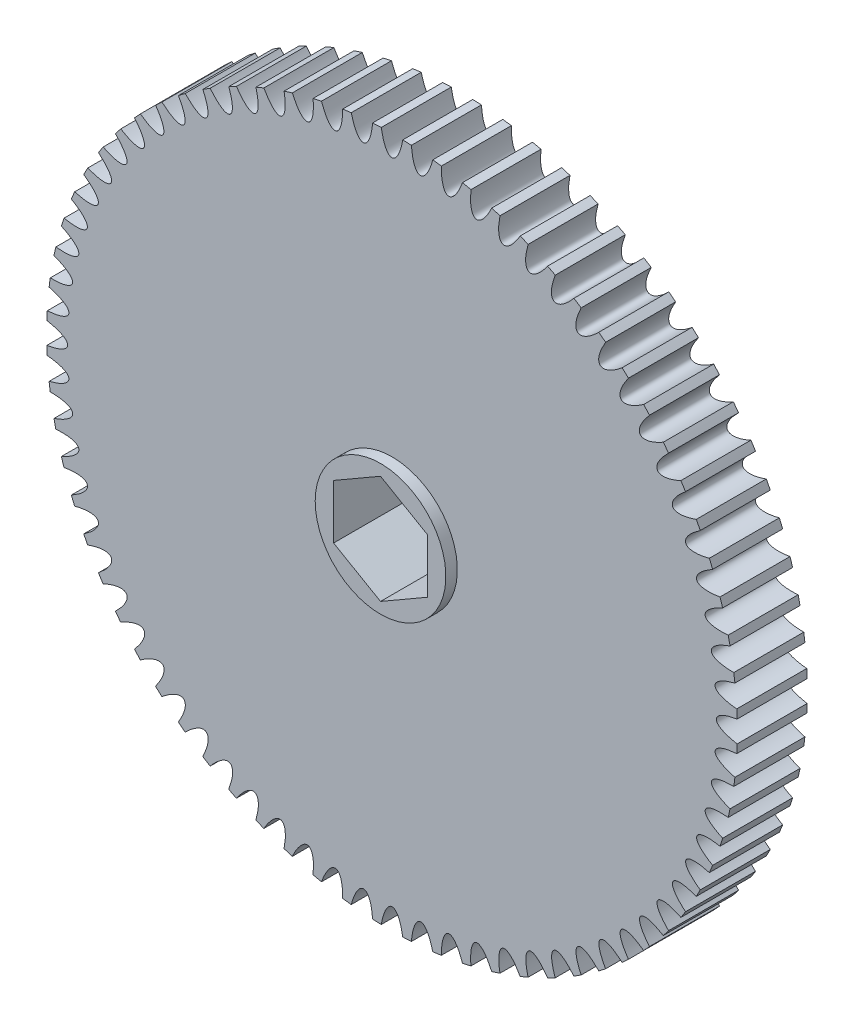
SolidWorks part; units mm, degrees
material "Vex Aluminum Spur Gear"
ref_plane "Front Plane" through (0, 0, 0) normal (0, 0, 1) x (1, 0, 0)
ref_plane "Top Plane" through (0, 0, 0) normal (0, 1, 0) x (1, 0, 0)
ref_plane "Right Plane" through (0, 0, 0) normal (1, 0, 0) x (0, 0, -1)
ref_plane "Plane1" through (0, 0, -4.7625) normal (0, 0, -1) x (-1, 0, 0)
sketch "Sketch1" plane through (0, 0, -4.7625) normal (0, 0, -1) x (-1, 0, 0)
  arc A0 (-46.916, 2.6363) -> (-46.9672, 1.4627) centre (0, 0) ccw
  arc A1 (-46.9672, -1.4627) -> (-46.916, -2.6363) centre (0, 0) ccw
  arc A2 (-46.661, -5.5506) -> (-46.5077, -6.7153) centre (0, 0) ccw
  arc A3 (-45.9997, -9.5963) -> (-45.7454, -10.7431) centre (0, 0) ccw
  arc A4 (-44.9883, -13.5689) -> (-44.635, -14.6892) centre (0, 0) ccw
  arc A5 (-43.6345, -17.4382) -> (-43.1849, -18.5235) centre (0, 0) ccw
  arc A6 (-41.9486, -21.1749) -> (-41.4062, -22.2169) centre (0, 0) ccw
  arc A7 (-39.9435, -24.7504) -> (-39.3123, -25.7411) centre (0, 0) ccw
  arc A8 (-37.6343, -28.1375) -> (-36.9192, -29.0694) centre (0, 0) ccw
  arc A9 (-35.0388, -31.3105) -> (-34.2451, -32.1765) centre (0, 0) ccw
  arc A10 (-32.1765, -34.2451) -> (-31.3105, -35.0388) centre (0, 0) ccw
  arc A11 (-29.0694, -36.9192) -> (-28.1375, -37.6343) centre (0, 0) ccw
  arc A12 (-25.7411, -39.3123) -> (-24.7504, -39.9435) centre (0, 0) ccw
  arc A13 (-22.2169, -41.4062) -> (-21.1749, -41.9486) centre (0, 0) ccw
  arc A14 (-18.5235, -43.1849) -> (-17.4382, -43.6345) centre (0, 0) ccw
  arc A15 (-14.6892, -44.635) -> (-13.5689, -44.9883) centre (0, 0) ccw
  arc A16 (-10.7431, -45.7454) -> (-9.5963, -45.9997) centre (0, 0) ccw
  arc A17 (-6.7153, -46.5077) -> (-5.5506, -46.661) centre (0, 0) ccw
  arc A18 (-2.6363, -46.916) -> (-1.4627, -46.9672) centre (0, 0) ccw
  arc A19 (1.4627, -46.9672) -> (2.6363, -46.916) centre (0, 0) ccw
  arc A20 (5.5506, -46.661) -> (6.7153, -46.5077) centre (0, 0) ccw
  arc A21 (9.5963, -45.9997) -> (10.7431, -45.7454) centre (0, 0) ccw
  arc A22 (13.5689, -44.9883) -> (14.6892, -44.635) centre (0, 0) ccw
  arc A23 (17.4382, -43.6345) -> (18.5235, -43.1849) centre (0, 0) ccw
  arc A24 (21.1749, -41.9486) -> (22.2169, -41.4062) centre (0, 0) ccw
  arc A25 (24.7504, -39.9435) -> (25.7411, -39.3123) centre (0, 0) ccw
  arc A26 (28.1375, -37.6343) -> (29.0694, -36.9192) centre (0, 0) ccw
  arc A27 (31.3105, -35.0388) -> (32.1765, -34.2451) centre (0, 0) ccw
  arc A28 (34.2451, -32.1765) -> (35.0388, -31.3105) centre (0, 0) ccw
  arc A29 (36.9192, -29.0694) -> (37.6343, -28.1375) centre (0, 0) ccw
  arc A30 (39.3123, -25.7411) -> (39.9435, -24.7504) centre (0, 0) ccw
  arc A31 (41.4062, -22.2169) -> (41.9486, -21.1749) centre (0, 0) ccw
  arc A32 (43.1849, -18.5235) -> (43.6345, -17.4382) centre (0, 0) ccw
  arc A33 (44.635, -14.6892) -> (44.9883, -13.5689) centre (0, 0) ccw
  arc A34 (45.7454, -10.7431) -> (45.9997, -9.5963) centre (0, 0) ccw
  arc A35 (46.5077, -6.7153) -> (46.661, -5.5506) centre (0, 0) ccw
  arc A36 (46.916, -2.6363) -> (46.9672, -1.4627) centre (0, 0) ccw
  arc A37 (46.9672, 1.4627) -> (46.916, 2.6363) centre (0, 0) ccw
  arc A38 (46.661, 5.5506) -> (46.5077, 6.7153) centre (0, 0) ccw
  arc A39 (45.9997, 9.5963) -> (45.7454, 10.7431) centre (0, 0) ccw
  arc A40 (44.9883, 13.5689) -> (44.635, 14.6892) centre (0, 0) ccw
  arc A41 (43.6345, 17.4382) -> (43.1849, 18.5235) centre (0, 0) ccw
  arc A42 (41.9486, 21.1749) -> (41.4062, 22.2169) centre (0, 0) ccw
  arc A43 (39.9435, 24.7504) -> (39.3123, 25.7411) centre (0, 0) ccw
  arc A44 (37.6343, 28.1375) -> (36.9192, 29.0694) centre (0, 0) ccw
  arc A45 (35.0388, 31.3105) -> (34.2451, 32.1765) centre (0, 0) ccw
  arc A46 (32.1765, 34.2451) -> (31.3105, 35.0388) centre (0, 0) ccw
  arc A47 (29.0694, 36.9192) -> (28.1375, 37.6343) centre (0, 0) ccw
  arc A48 (25.7411, 39.3123) -> (24.7504, 39.9435) centre (0, 0) ccw
  arc A49 (22.2169, 41.4062) -> (21.1749, 41.9486) centre (0, 0) ccw
  arc A50 (18.5235, 43.1849) -> (17.4382, 43.6345) centre (0, 0) ccw
  arc A51 (14.6892, 44.635) -> (13.5689, 44.9883) centre (0, 0) ccw
  arc A52 (10.7431, 45.7454) -> (9.5963, 45.9997) centre (0, 0) ccw
  arc A53 (6.7153, 46.5077) -> (5.5506, 46.661) centre (0, 0) ccw
  arc A54 (2.6363, 46.916) -> (1.4627, 46.9672) centre (0, 0) ccw
  arc A55 (-1.4627, 46.9672) -> (-2.6363, 46.916) centre (0, 0) ccw
  arc A56 (-5.5506, 46.661) -> (-6.7153, 46.5077) centre (0, 0) ccw
  arc A57 (-9.5963, 45.9997) -> (-10.7431, 45.7454) centre (0, 0) ccw
  arc A58 (-13.5689, 44.9883) -> (-14.6892, 44.635) centre (0, 0) ccw
  arc A59 (-17.4382, 43.6345) -> (-18.5235, 43.1849) centre (0, 0) ccw
  arc A60 (-21.1749, 41.9486) -> (-22.2169, 41.4062) centre (0, 0) ccw
  arc A61 (-24.7504, 39.9435) -> (-25.7411, 39.3123) centre (0, 0) ccw
  arc A62 (-28.1375, 37.6343) -> (-29.0694, 36.9192) centre (0, 0) ccw
  arc A63 (-31.3105, 35.0388) -> (-32.1765, 34.2451) centre (0, 0) ccw
  arc A64 (-34.2451, 32.1765) -> (-35.0388, 31.3105) centre (0, 0) ccw
  arc A65 (-36.9192, 29.0694) -> (-37.6343, 28.1375) centre (0, 0) ccw
  arc A66 (-39.3123, 25.7411) -> (-39.9435, 24.7504) centre (0, 0) ccw
  arc A67 (-41.4062, 22.2169) -> (-41.9486, 21.1749) centre (0, 0) ccw
  arc A68 (-43.1849, 18.5235) -> (-43.6345, 17.4382) centre (0, 0) ccw
  arc A69 (-44.635, 14.6892) -> (-44.9883, 13.5689) centre (0, 0) ccw
  arc A70 (-45.7454, 10.7431) -> (-45.9997, 9.5963) centre (0, 0) ccw
  arc A71 (-46.5077, 6.7153) -> (-46.661, 5.5506) centre (0, 0) ccw
  ellipse E0 centre (-49.5706, -0.0206) end of major axis (-55.0091, -0.068) minor radius 1.666 (-46.9672, -1.4627) -> (-46.9672, 1.4627) ccw
  ellipse E1 centre (-49.3802, -4.3409) end of major axis (-54.7938, -4.8621) minor radius 1.666 (-46.661, -5.5506) -> (-46.916, -2.6363) ccw
  ellipse E2 centre (-48.814, -8.6281) end of major axis (-54.1615, -9.6192) minor radius 1.666 (-45.9997, -9.5963) -> (-46.5077, -6.7153) ccw
  ellipse E3 centre (-47.8762, -12.8497) end of major axis (-53.1171, -14.303) minor radius 1.666 (-44.9883, -13.5689) -> (-45.7454, -10.7431) ccw
  ellipse E4 centre (-46.5741, -16.9735) end of major axis (-51.6684, -18.8781) minor radius 1.666 (-43.6345, -17.4382) -> (-44.635, -14.6892) ccw
  ellipse E5 centre (-44.9176, -20.9681) end of major axis (-49.8264, -23.3094) minor radius 1.666 (-41.9486, -21.1749) -> (-43.1849, -18.5235) ccw
  ellipse E6 centre (-42.9191, -24.8031) end of major axis (-47.6053, -27.5634) minor radius 1.666 (-39.9435, -24.7504) -> (-41.4062, -22.2169) ccw
  ellipse E7 centre (-40.5941, -28.4494) end of major axis (-45.0218, -31.6076) minor radius 1.666 (-37.6343, -28.1375) -> (-39.3123, -25.7411) ccw
  ellipse E8 centre (-37.9601, -31.8791) end of major axis (-42.0957, -35.4112) minor radius 1.666 (-35.0388, -31.3105) -> (-36.9192, -29.0694) ccw
  ellipse E9 centre (-35.0372, -35.0663) end of major axis (-31.2252, -31.1872) minor radius 1.666 (-32.1765, -34.2451) -> (-34.2451, -32.1765) ccw
  ellipse E10 centre (-31.8476, -37.9865) end of major axis (-35.3071, -42.1831) minor radius 1.666 (-29.0694, -36.9192) -> (-31.3105, -35.0388) ccw
  ellipse E11 centre (-28.4157, -40.6177) end of major axis (-31.4962, -45.0998) minor radius 1.666 (-25.7411, -39.3123) -> (-28.1375, -37.6343) ccw
  ellipse E12 centre (-24.7675, -42.9397) end of major axis (-22.0894, -38.2062) minor radius 1.666 (-22.2169, -41.4062) -> (-24.7504, -39.9435) ccw
  ellipse E13 centre (-20.9308, -44.9349) end of major axis (-18.6754, -39.986) minor radius 1.666 (-18.5235, -43.1849) -> (-21.1749, -41.9486) ccw
  ellipse E14 centre (-16.9348, -46.5882) end of major axis (-15.1193, -41.4615) minor radius 1.666 (-14.6892, -44.635) -> (-17.4382, -43.6345) ccw
  ellipse E15 centre (-12.81, -47.8869) end of major axis (-11.4482, -42.6215) minor radius 1.666 (-10.7431, -45.7454) -> (-13.5689, -44.9883) ccw
  ellipse E16 centre (-8.5876, -48.8211) end of major axis (-7.6899, -43.4571) minor radius 1.666 (-6.7153, -46.5077) -> (-9.5963, -45.9997) ccw
  ellipse E17 centre (-4.2999, -49.3838) end of major axis (-3.8731, -43.9619) minor radius 1.666 (-2.6363, -46.916) -> (-5.5506, -46.661) ccw
  ellipse E18 centre (0.0206, -49.5706) end of major axis (-0.0268, -44.1322) minor radius 1.666 (1.4627, -46.9672) -> (-1.4627, -46.9672) ccw
  ellipse E19 centre (4.3409, -49.3802) end of major axis (3.8196, -43.9666) minor radius 1.666 (5.5506, -46.661) -> (2.6363, -46.916) ccw
  ellipse E20 centre (8.6281, -48.814) end of major axis (9.6192, -54.1615) minor radius 1.666 (9.5963, -45.9997) -> (6.7153, -46.5077) ccw
  ellipse E21 centre (12.8497, -47.8762) end of major axis (11.3963, -42.6354) minor radius 1.666 (13.5689, -44.9883) -> (10.7431, -45.7454) ccw
  ellipse E22 centre (16.9735, -46.5741) end of major axis (15.0689, -41.4799) minor radius 1.666 (17.4382, -43.6345) -> (14.6892, -44.635) ccw
  ellipse E23 centre (20.9681, -44.9176) end of major axis (18.6268, -40.0087) minor radius 1.666 (21.1749, -41.9486) -> (18.5235, -43.1849) ccw
  ellipse E24 centre (24.8031, -42.9191) end of major axis (22.0429, -38.233) minor radius 1.666 (24.7504, -39.9435) -> (22.2169, -41.4062) ccw
  ellipse E25 centre (28.4494, -40.5941) end of major axis (25.2912, -36.1664) minor radius 1.666 (28.1375, -37.6343) -> (25.7411, -39.3123) ccw
  ellipse E26 centre (31.8791, -37.9601) end of major axis (28.3471, -33.8245) minor radius 1.666 (31.3105, -35.0388) -> (29.0694, -36.9192) ccw
  ellipse E27 centre (35.0663, -35.0372) end of major axis (31.1872, -31.2252) minor radius 1.666 (34.2451, -32.1765) -> (32.1765, -34.2451) ccw
  ellipse E28 centre (37.9865, -31.8476) end of major axis (33.79, -28.3882) minor radius 1.666 (36.9192, -29.0694) -> (35.0388, -31.3105) ccw
  ellipse E29 centre (40.6177, -28.4157) end of major axis (36.1356, -25.3352) minor radius 1.666 (39.3123, -25.7411) -> (37.6343, -28.1375) ccw
  ellipse E30 centre (42.9397, -24.7675) end of major axis (38.2062, -22.0894) minor radius 1.666 (41.4062, -22.2169) -> (39.9435, -24.7504) ccw
  ellipse E31 centre (44.9349, -20.9308) end of major axis (39.986, -18.6754) minor radius 1.666 (43.1849, -18.5235) -> (41.9486, -21.1749) ccw
  ellipse E32 centre (46.5882, -16.9348) end of major axis (41.4615, -15.1193) minor radius 1.666 (44.635, -14.6892) -> (43.6345, -17.4382) ccw
  ellipse E33 centre (47.8869, -12.81) end of major axis (42.6215, -11.4482) minor radius 1.666 (45.7454, -10.7431) -> (44.9883, -13.5689) ccw
  ellipse E34 centre (48.8211, -8.5876) end of major axis (43.4571, -7.6899) minor radius 1.666 (46.5077, -6.7153) -> (45.9997, -9.5963) ccw
  ellipse E35 centre (49.3838, -4.2999) end of major axis (43.9619, -3.8731) minor radius 1.666 (46.916, -2.6363) -> (46.661, -5.5506) ccw
  ellipse E36 centre (49.5706, 0.0206) end of major axis (44.1322, -0.0268) minor radius 1.666 (46.9672, 1.4627) -> (46.9672, -1.4627) ccw
  ellipse E37 centre (49.3802, 4.3409) end of major axis (43.9666, 3.8196) minor radius 1.666 (46.661, 5.5506) -> (46.916, 2.6363) ccw
  ellipse E38 centre (48.814, 8.6281) end of major axis (43.4664, 7.637) minor radius 1.666 (45.9997, 9.5963) -> (46.5077, 6.7153) ccw
  ellipse E39 centre (47.8762, 12.8497) end of major axis (42.6354, 11.3963) minor radius 1.666 (44.9883, 13.5689) -> (45.7454, 10.7431) ccw
  ellipse E40 centre (46.5741, 16.9735) end of major axis (41.4799, 15.0689) minor radius 1.666 (43.6345, 17.4382) -> (44.635, 14.6892) ccw
  ellipse E41 centre (44.9176, 20.9681) end of major axis (40.0087, 18.6268) minor radius 1.666 (41.9486, 21.1749) -> (43.1849, 18.5235) ccw
  ellipse E42 centre (42.9191, 24.8031) end of major axis (38.233, 22.0429) minor radius 1.666 (39.9435, 24.7504) -> (41.4062, 22.2169) ccw
  ellipse E43 centre (40.5941, 28.4494) end of major axis (36.1664, 25.2912) minor radius 1.666 (37.6343, 28.1375) -> (39.3123, 25.7411) ccw
  ellipse E44 centre (37.9601, 31.8791) end of major axis (33.8245, 28.3471) minor radius 1.666 (35.0388, 31.3105) -> (36.9192, 29.0694) ccw
  ellipse E45 centre (35.0372, 35.0663) end of major axis (38.8492, 38.9453) minor radius 1.666 (32.1765, 34.2451) -> (34.2451, 32.1765) ccw
  ellipse E46 centre (31.8476, 37.9865) end of major axis (35.3071, 42.1831) minor radius 1.666 (29.0694, 36.9192) -> (31.3105, 35.0388) ccw
  ellipse E47 centre (28.4157, 40.6177) end of major axis (31.4962, 45.0998) minor radius 1.666 (25.7411, 39.3123) -> (28.1375, 37.6343) ccw
  ellipse E48 centre (24.7675, 42.9397) end of major axis (27.4457, 47.6732) minor radius 1.666 (22.2169, 41.4062) -> (24.7504, 39.9435) ccw
  ellipse E49 centre (20.9308, 44.9349) end of major axis (23.1862, 49.8839) minor radius 1.666 (18.5235, 43.1849) -> (21.1749, 41.9486) ccw
  ellipse E50 centre (16.9348, 46.5882) end of major axis (18.7503, 51.7148) minor radius 1.666 (14.6892, 44.635) -> (17.4382, 43.6345) ccw
  ellipse E51 centre (12.81, 47.8869) end of major axis (14.1717, 53.1523) minor radius 1.666 (10.7431, 45.7454) -> (13.5689, 44.9883) ccw
  ellipse E52 centre (8.5876, 48.8211) end of major axis (9.4853, 54.1851) minor radius 1.666 (6.7153, 46.5077) -> (9.5963, 45.9997) ccw
  ellipse E53 centre (4.2999, 49.3838) end of major axis (4.7266, 54.8057) minor radius 1.666 (2.6363, 46.916) -> (5.5506, 46.661) ccw
  ellipse E54 centre (-0.0206, 49.5706) end of major axis (-0.068, 55.0091) minor radius 1.666 (-1.4627, 46.9672) -> (1.4627, 46.9672) ccw
  ellipse E55 centre (-4.3409, 49.3802) end of major axis (-4.8621, 54.7938) minor radius 1.666 (-5.5506, 46.661) -> (-2.6363, 46.916) ccw
  ellipse E56 centre (-8.6281, 48.814) end of major axis (-9.6192, 54.1615) minor radius 1.666 (-9.5963, 45.9997) -> (-6.7153, 46.5077) ccw
  ellipse E57 centre (-12.8497, 47.8762) end of major axis (-14.303, 53.1171) minor radius 1.666 (-13.5689, 44.9883) -> (-10.7431, 45.7454) ccw
  ellipse E58 centre (-16.9735, 46.5741) end of major axis (-18.8781, 51.6684) minor radius 1.666 (-17.4382, 43.6345) -> (-14.6892, 44.635) ccw
  ellipse E59 centre (-20.9681, 44.9176) end of major axis (-23.3094, 49.8264) minor radius 1.666 (-21.1749, 41.9486) -> (-18.5235, 43.1849) ccw
  ellipse E60 centre (-24.8031, 42.9191) end of major axis (-27.5634, 47.6053) minor radius 1.666 (-24.7504, 39.9435) -> (-22.2169, 41.4062) ccw
  ellipse E61 centre (-28.4494, 40.5941) end of major axis (-31.6076, 45.0218) minor radius 1.666 (-28.1375, 37.6343) -> (-25.7411, 39.3123) ccw
  ellipse E62 centre (-31.8791, 37.9601) end of major axis (-35.4112, 42.0957) minor radius 1.666 (-31.3105, 35.0388) -> (-29.0694, 36.9192) ccw
  ellipse E63 centre (-35.0663, 35.0372) end of major axis (-38.9453, 38.8492) minor radius 1.666 (-34.2451, 32.1765) -> (-32.1765, 34.2451) ccw
  ellipse E64 centre (-37.9865, 31.8476) end of major axis (-42.1831, 35.3071) minor radius 1.666 (-36.9192, 29.0694) -> (-35.0388, 31.3105) ccw
  ellipse E65 centre (-40.6177, 28.4157) end of major axis (-45.0998, 31.4962) minor radius 1.666 (-39.3123, 25.7411) -> (-37.6343, 28.1375) ccw
  ellipse E66 centre (-42.9397, 24.7675) end of major axis (-47.6732, 27.4457) minor radius 1.666 (-41.4062, 22.2169) -> (-39.9435, 24.7504) ccw
  ellipse E67 centre (-44.9349, 20.9308) end of major axis (-49.8839, 23.1862) minor radius 1.666 (-43.1849, 18.5235) -> (-41.9486, 21.1749) ccw
  ellipse E68 centre (-46.5882, 16.9348) end of major axis (-51.7148, 18.7503) minor radius 1.666 (-44.635, 14.6892) -> (-43.6345, 17.4382) ccw
  ellipse E69 centre (-47.8869, 12.81) end of major axis (-53.1523, 14.1717) minor radius 1.666 (-45.7454, 10.7431) -> (-44.9883, 13.5689) ccw
  ellipse E70 centre (-48.8211, 8.5876) end of major axis (-54.1851, 9.4853) minor radius 1.666 (-46.5077, 6.7153) -> (-45.9997, 9.5963) ccw
  ellipse E71 centre (-49.3838, 4.2999) end of major axis (-54.8057, 4.7266) minor radius 1.666 (-46.916, 2.6363) -> (-46.661, 5.5506) ccw
  point P3 (-49.5706, -0.0206)
  point P4 (-55.0091, -0.068)
  point P5 (-49.5852, 1.6453)
  point P6 (-46.9672, -1.4627)
  point P7 (-46.9672, 1.4627)
  point P8 (-44.1447, -0.0587)
  point P9 (-54.9965, 0.0176)
  point P17 (-49.3802, -4.3409)
  point P18 (-54.7938, -4.8621)
  point P19 (-49.5399, -2.6826)
  point P20 (-46.661, -5.5506)
  point P21 (-46.916, -2.6363)
  point P22 (-43.9716, -3.9059)
  point P23 (-54.7888, -4.7758)
  point P31 (-48.814, -8.6281)
  point P32 (-54.1615, -9.6192)
  point P33 (-49.1176, -6.99)
  point P34 (-45.9997, -9.5963)
  point P35 (-46.5077, -6.7153)
  point P36 (-43.4639, -7.7234)
  point P37 (-54.1641, -9.5328)
  point P45 (-47.8762, -12.8497)
  point P46 (-53.1171, -14.303)
  point P47 (-48.3214, -11.2443)
  point P48 (-44.9883, -13.5689)
  point P49 (-45.7454, -10.7431)
  point P50 (-42.6253, -11.4822)
  point P51 (-53.1271, -14.2172)
  point P59 (-46.5741, -16.9735)
  point P60 (-51.6684, -18.8781)
  point P61 (-47.1575, -15.413)
  point P62 (-43.6345, -17.4382)
  point P63 (-44.635, -14.6892)
  point P64 (-41.4624, -15.1535)
  point P65 (-51.6859, -18.7934)
  point P73 (-44.9176, -20.9681)
  point P74 (-49.8264, -23.3094)
  point P75 (-45.6348, -19.4644)
  point P76 (-41.9486, -21.1749)
  point P77 (-43.1849, -18.5235)
  point P78 (-39.9839, -18.7096)
  point P79 (-49.8512, -23.2266)
  point P87 (-42.9191, -24.8031)
  point P88 (-47.6053, -27.5634)
  point P89 (-43.7647, -23.3677)
  point P90 (-39.9435, -24.7504)
  point P91 (-41.4062, -22.2169)
  point P92 (-38.2011, -22.1232)
  point P93 (-47.6372, -27.4831)
  point P101 (-40.5941, -28.4494)
  point P102 (-45.0218, -31.6076)
  point P103 (-41.5615, -27.0931)
  point P104 (-37.6343, -28.1375)
  point P105 (-39.3123, -25.7411)
  point P106 (-36.1276, -25.3684)
  point P107 (-45.0606, -31.5303)
  point P115 (-37.9601, -31.8791)
  point P116 (-42.0957, -35.4112)
  point P117 (-39.042, -30.6123)
  point P118 (-35.0388, -31.3105)
  point P119 (-36.9192, -29.0694)
  point P120 (-33.7791, -28.4206)
  point P121 (-42.1411, -35.3377)
  point P129 (-35.0372, -35.0663)
  point P130 (-36.2254, -33.8986)
  point P131 (-31.2252, -31.1872)
  point P132 (-32.1765, -34.2451)
  point P133 (-34.2451, -32.1765)
  point P134 (-31.1735, -31.2565)
  point P135 (-38.9008, -38.876)
  point P143 (-31.8476, -37.9865)
  point P144 (-33.1331, -36.9268)
  point P145 (-28.3882, -33.79)
  point P146 (-29.0694, -36.9192)
  point P147 (-31.3105, -35.0388)
  point P148 (-28.3307, -33.8545)
  point P149 (-35.3645, -42.1185)
  point P157 (-28.4157, -40.6177)
  point P158 (-29.7886, -39.6741)
  point P159 (-25.3352, -36.1356)
  point P160 (-25.7411, -39.3123)
  point P161 (-28.1375, -37.6343)
  point P162 (-25.2723, -36.1949)
  point P163 (-31.5591, -45.0405)
  point P171 (-24.7675, -42.9397)
  point P172 (-26.2175, -42.1193)
  point P173 (-22.0894, -38.2062)
  point P174 (-22.2169, -41.4062)
  point P175 (-24.7504, -39.9435)
  point P176 (-22.0215, -38.2598)
  point P177 (-27.5135, -47.6196)
  point P185 (-20.9308, -44.9349)
  point P186 (-22.4468, -44.2441)
  point P187 (-18.6754, -39.986)
  point P188 (-18.5235, -43.1849)
  point P189 (-21.1749, -41.9486)
  point P190 (-18.6032, -40.0335)
  point P191 (-23.2585, -49.8364)
  point P199 (-16.9348, -46.5882)
  point P200 (-18.5052, -46.0321)
  point P201 (-15.1193, -41.4615)
  point P202 (-14.6892, -44.635)
  point P203 (-17.4382, -43.6345)
  point P204 (-15.0432, -41.5025)
  point P205 (-18.8264, -51.6738)
  point P213 (-12.81, -47.8869)
  point P214 (-14.4228, -47.4697)
  point P215 (-11.4482, -42.6215)
  point P216 (-10.7431, -45.7454)
  point P217 (-13.5689, -44.9883)
  point P218 (-11.3688, -42.6557)
  point P219 (-14.2511, -53.118)
  point P227 (-8.5876, -48.8211)
  point P228 (-10.2307, -48.5461)
  point P229 (-7.6899, -43.4571)
  point P230 (-6.7153, -46.5077)
  point P231 (-9.5963, -45.9997)
  point P232 (-7.6079, -43.4843)
  point P233 (-9.5673, -54.158)
  point P241 (-4.2999, -49.3838)
  point P242 (-5.9607, -49.2531)
  point P243 (-3.8731, -43.9619)
  point P244 (-2.6363, -46.916)
  point P245 (-5.5506, -46.661)
  point P246 (-3.789, -43.9819)
  point P247 (-4.8108, -54.7857)
  point P255 (0.0206, -49.5706)
  point P256 (-1.6453, -49.5852)
  point P257 (-0.0268, -44.1322)
  point P258 (1.4627, -46.9672)
  point P259 (-1.4627, -46.9672)
  point P260 (0.0587, -44.1447)
  point P261 (-0.0176, -54.9965)
  point P269 (4.3409, -49.3802)
  point P270 (2.6826, -49.5399)
  point P271 (3.8196, -43.9666)
  point P272 (5.5506, -46.661)
  point P273 (2.6363, -46.916)
  point P274 (3.9059, -43.9716)
  point P275 (4.7758, -54.7888)
  point P283 (8.6281, -48.814)
  point P284 (6.99, -49.1176)
  point P285 (7.637, -43.4664)
  point P286 (9.5963, -45.9997)
  point P287 (6.7153, -46.5077)
  point P288 (7.7234, -43.4639)
  point P289 (9.5328, -54.1641)
  point P297 (12.8497, -47.8762)
  point P298 (11.2443, -48.3214)
  point P299 (11.3963, -42.6354)
  point P300 (13.5689, -44.9883)
  point P301 (10.7431, -45.7454)
  point P302 (11.4822, -42.6253)
  point P303 (14.2172, -53.1271)
  point P311 (16.9735, -46.5741)
  point P312 (15.413, -47.1575)
  point P313 (15.0689, -41.4799)
  point P314 (17.4382, -43.6345)
  point P315 (14.6892, -44.635)
  point P316 (15.1535, -41.4624)
  point P317 (18.7934, -51.6859)
  point P325 (20.9681, -44.9176)
  point P326 (19.4644, -45.6348)
  point P327 (18.6268, -40.0087)
  point P328 (21.1749, -41.9486)
  point P329 (18.5235, -43.1849)
  point P330 (18.7096, -39.9839)
  point P331 (23.2266, -49.8512)
  point P339 (24.8031, -42.9191)
  point P340 (23.3677, -43.7647)
  point P341 (22.0429, -38.233)
  point P342 (24.7504, -39.9435)
  point P343 (22.2169, -41.4062)
  point P344 (22.1232, -38.2011)
  point P345 (27.4831, -47.6372)
  point P353 (28.4494, -40.5941)
  point P354 (27.0931, -41.5615)
  point P355 (25.2912, -36.1664)
  point P356 (28.1375, -37.6343)
  point P357 (25.7411, -39.3123)
  point P358 (25.3684, -36.1276)
  point P359 (31.5303, -45.0606)
  point P367 (31.8791, -37.9601)
  point P368 (30.6123, -39.042)
  point P369 (28.3471, -33.8245)
  point P370 (31.3105, -35.0388)
  point P371 (29.0694, -36.9192)
  point P372 (28.4206, -33.7791)
  point P373 (35.3377, -42.1411)
  point P381 (35.0663, -35.0372)
  point P382 (31.1872, -31.2252)
  point P383 (36.234, -33.849)
  point P384 (34.2451, -32.1765)
  point P385 (32.1765, -34.2451)
  point P386 (31.2565, -31.1735)
  point P387 (38.876, -38.9008)
  point P395 (37.9865, -31.8476)
  point P396 (33.79, -28.3882)
  point P397 (39.0462, -30.5622)
  point P398 (36.9192, -29.0694)
  point P399 (35.0388, -31.3105)
  point P400 (33.8545, -28.3307)
  point P401 (42.1185, -35.3645)
  point P409 (40.6177, -28.4157)
  point P410 (36.1356, -25.3352)
  point P411 (41.5613, -27.0428)
  point P412 (39.3123, -25.7411)
  point P413 (37.6343, -28.1375)
  point P414 (36.1949, -25.2723)
  point P415 (45.0405, -31.5591)
  point P423 (42.9397, -24.7675)
  point P424 (38.2062, -22.0894)
  point P425 (43.7601, -23.3175)
  point P426 (41.4062, -22.2169)
  point P427 (39.9435, -24.7504)
  point P428 (38.2598, -22.0215)
  point P429 (47.6196, -27.5135)
  point P437 (44.9349, -20.9308)
  point P438 (39.986, -18.6754)
  point P439 (45.6258, -19.4149)
  point P440 (43.1849, -18.5235)
  point P441 (41.9486, -21.1749)
  point P442 (40.0335, -18.6032)
  point P443 (49.8364, -23.2585)
  point P451 (46.5882, -16.9348)
  point P452 (41.4615, -15.1193)
  point P453 (47.1443, -15.3644)
  point P454 (44.635, -14.6892)
  point P455 (43.6345, -17.4382)
  point P456 (41.5025, -15.0432)
  point P457 (51.6738, -18.8264)
  point P465 (47.8869, -12.81)
  point P466 (42.6215, -11.4482)
  point P467 (48.304, -11.1971)
  point P468 (45.7454, -10.7431)
  point P469 (44.9883, -13.5689)
  point P470 (42.6557, -11.3688)
  point P471 (53.118, -14.2511)
  point P479 (48.8211, -8.5876)
  point P480 (43.4571, -7.6899)
  point P481 (49.0961, -6.9445)
  point P482 (46.5077, -6.7153)
  point P483 (45.9997, -9.5963)
  point P484 (43.4843, -7.6079)
  point P485 (54.158, -9.5673)
  point P493 (49.3838, -4.2999)
  point P494 (43.9619, -3.8731)
  point P495 (49.5145, -2.6391)
  point P496 (46.916, -2.6363)
  point P497 (46.661, -5.5506)
  point P498 (43.9819, -3.789)
  point P499 (54.7857, -4.8108)
  point P507 (49.5706, 0.0206)
  point P508 (44.1322, -0.0268)
  point P509 (49.5561, 1.6865)
  point P510 (46.9672, 1.4627)
  point P511 (46.9672, -1.4627)
  point P512 (44.1447, 0.0587)
  point P513 (54.9965, -0.0176)
  point P521 (49.3802, 4.3409)
  point P522 (43.9666, 3.8196)
  point P523 (49.2206, 5.9991)
  point P524 (46.661, 5.5506)
  point P525 (46.916, 2.6363)
  point P526 (43.9716, 3.9059)
  point P527 (54.7888, 4.7758)
  point P535 (48.814, 8.6281)
  point P536 (43.4664, 7.637)
  point P537 (48.5104, 10.2662)
  point P538 (45.9997, 9.5963)
  point P539 (46.5077, 6.7153)
  point P540 (43.4639, 7.7234)
  point P541 (54.1641, 9.5328)
  point P549 (47.8762, 12.8497)
  point P550 (42.6354, 11.3963)
  point P551 (47.431, 14.4551)
  point P552 (44.9883, 13.5689)
  point P553 (45.7454, 10.7431)
  point P554 (42.6253, 11.4822)
  point P555 (53.1271, 14.2172)
  point P563 (46.5741, 16.9735)
  point P564 (41.4799, 15.0689)
  point P565 (45.9907, 18.5339)
  point P566 (43.6345, 17.4382)
  point P567 (44.635, 14.6892)
  point P568 (41.4624, 15.1535)
  point P569 (51.6859, 18.7934)
  point P577 (44.9176, 20.9681)
  point P578 (40.0087, 18.6268)
  point P579 (44.2004, 22.4718)
  point P580 (41.9486, 21.1749)
  point P581 (43.1849, 18.5235)
  point P582 (39.9839, 18.7096)
  point P583 (49.8512, 23.2266)
  point P591 (42.9191, 24.8031)
  point P592 (38.233, 22.0429)
  point P593 (42.0736, 26.2386)
  point P594 (39.9435, 24.7504)
  point P595 (41.4062, 22.2169)
  point P596 (38.2011, 22.1232)
  point P597 (47.6372, 27.4831)
  point P605 (40.5941, 28.4494)
  point P606 (36.1664, 25.2912)
  point P607 (39.6267, 29.8057)
  point P608 (37.6343, 28.1375)
  point P609 (39.3123, 25.7411)
  point P610 (36.1276, 25.3684)
  point P611 (45.0606, 31.5303)
  point P619 (37.9601, 31.8791)
  point P620 (33.8245, 28.3471)
  point P621 (36.8782, 33.146)
  point P622 (35.0388, 31.3105)
  point P623 (36.9192, 29.0694)
  point P624 (33.7791, 28.4206)
  point P625 (42.1411, 35.3377)
  point P633 (35.0372, 35.0663)
  point P634 (33.849, 36.234)
  point P635 (38.8492, 38.9453)
  point P636 (32.1765, 34.2451)
  point P637 (34.2451, 32.1765)
  point P638 (31.1735, 31.2565)
  point P639 (38.9008, 38.876)
  point P647 (31.8476, 37.9865)
  point P648 (30.5622, 39.0462)
  point P649 (35.3071, 42.1831)
  point P650 (29.0694, 36.9192)
  point P651 (31.3105, 35.0388)
  point P652 (28.3307, 33.8545)
  point P653 (35.3645, 42.1185)
  point P661 (28.4157, 40.6177)
  point P662 (27.0428, 41.5613)
  point P663 (31.4962, 45.0998)
  point P664 (25.7411, 39.3123)
  point P665 (28.1375, 37.6343)
  point P666 (25.2723, 36.1949)
  point P667 (31.5591, 45.0405)
  point P675 (24.7675, 42.9397)
  point P676 (23.3175, 43.7601)
  point P677 (27.4457, 47.6732)
  point P678 (22.2169, 41.4062)
  point P679 (24.7504, 39.9435)
  point P680 (22.0215, 38.2598)
  point P681 (27.5135, 47.6196)
  point P689 (20.9308, 44.9349)
  point P690 (19.4149, 45.6258)
  point P691 (23.1862, 49.8839)
  point P692 (18.5235, 43.1849)
  point P693 (21.1749, 41.9486)
  point P694 (18.6032, 40.0335)
  point P695 (23.2585, 49.8364)
  point P703 (16.9348, 46.5882)
  point P704 (15.3644, 47.1443)
  point P705 (18.7503, 51.7148)
  point P706 (14.6892, 44.635)
  point P707 (17.4382, 43.6345)
  point P708 (15.0432, 41.5025)
  point P709 (18.8264, 51.6738)
  point P717 (12.81, 47.8869)
  point P718 (11.1971, 48.304)
  point P719 (14.1717, 53.1523)
  point P720 (10.7431, 45.7454)
  point P721 (13.5689, 44.9883)
  point P722 (11.3688, 42.6557)
  point P723 (14.2511, 53.118)
  point P731 (8.5876, 48.8211)
  point P732 (6.9445, 49.0961)
  point P733 (9.4853, 54.1851)
  point P734 (6.7153, 46.5077)
  point P735 (9.5963, 45.9997)
  point P736 (7.6079, 43.4843)
  point P737 (9.5673, 54.158)
  point P745 (4.2999, 49.3838)
  point P746 (2.6391, 49.5145)
  point P747 (4.7266, 54.8057)
  point P748 (2.6363, 46.916)
  point P749 (5.5506, 46.661)
  point P750 (3.789, 43.9819)
  point P751 (4.8108, 54.7857)
  point P759 (-0.0206, 49.5706)
  point P760 (-1.6865, 49.5561)
  point P761 (-0.068, 55.0091)
  point P762 (-1.4627, 46.9672)
  point P763 (1.4627, 46.9672)
  point P764 (-0.0587, 44.1447)
  point P765 (0.0176, 54.9965)
  point P773 (-4.3409, 49.3802)
  point P774 (-5.9991, 49.2206)
  point P775 (-4.8621, 54.7938)
  point P776 (-5.5506, 46.661)
  point P777 (-2.6363, 46.916)
  point P778 (-3.9059, 43.9716)
  point P779 (-4.7758, 54.7888)
  point P787 (-8.6281, 48.814)
  point P788 (-10.2662, 48.5104)
  point P789 (-9.6192, 54.1615)
  point P790 (-9.5963, 45.9997)
  point P791 (-6.7153, 46.5077)
  point P792 (-7.7234, 43.4639)
  point P793 (-9.5328, 54.1641)
  point P801 (-12.8497, 47.8762)
  point P802 (-14.4551, 47.431)
  point P803 (-14.303, 53.1171)
  point P804 (-13.5689, 44.9883)
  point P805 (-10.7431, 45.7454)
  point P806 (-11.4822, 42.6253)
  point P807 (-14.2172, 53.1271)
  point P815 (-16.9735, 46.5741)
  point P816 (-18.5339, 45.9907)
  point P817 (-18.8781, 51.6684)
  point P818 (-17.4382, 43.6345)
  point P819 (-14.6892, 44.635)
  point P820 (-15.1535, 41.4624)
  point P821 (-18.7934, 51.6859)
  point P829 (-20.9681, 44.9176)
  point P830 (-22.4718, 44.2004)
  point P831 (-23.3094, 49.8264)
  point P832 (-21.1749, 41.9486)
  point P833 (-18.5235, 43.1849)
  point P834 (-18.7096, 39.9839)
  point P835 (-23.2266, 49.8512)
  point P843 (-24.8031, 42.9191)
  point P844 (-26.2386, 42.0736)
  point P845 (-27.5634, 47.6053)
  point P846 (-24.7504, 39.9435)
  point P847 (-22.2169, 41.4062)
  point P848 (-22.1232, 38.2011)
  point P849 (-27.4831, 47.6372)
  point P857 (-28.4494, 40.5941)
  point P858 (-29.8057, 39.6267)
  point P859 (-31.6076, 45.0218)
  point P860 (-28.1375, 37.6343)
  point P861 (-25.7411, 39.3123)
  point P862 (-25.3684, 36.1276)
  point P863 (-31.5303, 45.0606)
  point P871 (-31.8791, 37.9601)
  point P872 (-33.146, 36.8782)
  point P873 (-35.4112, 42.0957)
  point P874 (-31.3105, 35.0388)
  point P875 (-29.0694, 36.9192)
  point P876 (-28.4206, 33.7791)
  point P877 (-35.3377, 42.1411)
  point P885 (-35.0663, 35.0372)
  point P886 (-38.9453, 38.8492)
  point P887 (-33.8986, 36.2254)
  point P888 (-34.2451, 32.1765)
  point P889 (-32.1765, 34.2451)
  point P890 (-31.2565, 31.1735)
  point P891 (-38.876, 38.9008)
  point P899 (-37.9865, 31.8476)
  point P900 (-42.1831, 35.3071)
  point P901 (-36.9268, 33.1331)
  point P902 (-36.9192, 29.0694)
  point P903 (-35.0388, 31.3105)
  point P904 (-33.8545, 28.3307)
  point P905 (-42.1185, 35.3645)
  point P913 (-40.6177, 28.4157)
  point P914 (-45.0998, 31.4962)
  point P915 (-39.6741, 29.7886)
  point P916 (-39.3123, 25.7411)
  point P917 (-37.6343, 28.1375)
  point P918 (-36.1949, 25.2723)
  point P919 (-45.0405, 31.5591)
  point P927 (-42.9397, 24.7675)
  point P928 (-47.6732, 27.4457)
  point P929 (-42.1193, 26.2175)
  point P930 (-41.4062, 22.2169)
  point P931 (-39.9435, 24.7504)
  point P932 (-38.2598, 22.0215)
  point P933 (-47.6196, 27.5135)
  point P941 (-44.9349, 20.9308)
  point P942 (-49.8839, 23.1862)
  point P943 (-44.2441, 22.4468)
  point P944 (-43.1849, 18.5235)
  point P945 (-41.9486, 21.1749)
  point P946 (-40.0335, 18.6032)
  point P947 (-49.8364, 23.2585)
  point P955 (-46.5882, 16.9348)
  point P956 (-51.7148, 18.7503)
  point P957 (-46.0321, 18.5052)
  point P958 (-44.635, 14.6892)
  point P959 (-43.6345, 17.4382)
  point P960 (-41.5025, 15.0432)
  point P961 (-51.6738, 18.8264)
  point P969 (-47.8869, 12.81)
  point P970 (-53.1523, 14.1717)
  point P971 (-47.4697, 14.4228)
  point P972 (-45.7454, 10.7431)
  point P973 (-44.9883, 13.5689)
  point P974 (-42.6557, 11.3688)
  point P975 (-53.118, 14.2511)
  point P983 (-48.8211, 8.5876)
  point P984 (-54.1851, 9.4853)
  point P985 (-48.5461, 10.2307)
  point P986 (-46.5077, 6.7153)
  point P987 (-45.9997, 9.5963)
  point P988 (-43.4843, 7.6079)
  point P989 (-54.158, 9.5673)
  point P997 (-49.3838, 4.2999)
  point P998 (-54.8057, 4.7266)
  point P999 (-49.2531, 5.9607)
  point P1000 (-46.916, 2.6363)
  point P1001 (-46.661, 5.5506)
  point P1002 (-43.9819, 3.789)
  point P1003 (-54.7857, 4.8108)
extrude "Boss-Extrude1" add sketch "Sketch1" against normal blind 9.525
sketch "Sketch2" plane through (0, 0, -4.7625) normal (0, 0, -1) x (-1, 0, 0)
  circle A0 centre (0, 0) radius 8.89
extrude "Boss-Extrude2" add sketch "Sketch2" along normal blind 1.5621
sketch "Sketch3" plane through (0, 0, 4.7625) normal (0, 0, 1) x (1, 0, 0)
  circle A0 centre (0, 0) radius 8.89
extrude "Boss-Extrude3" add sketch "Sketch3" along normal blind 1.5621
sketch "Sketch4" plane through (0, 0, 6.3246) normal (0, 0, 1) x (1, 0, 0)
  line L0 (6.3881, -3.6882) -> (6.3881, 3.6882)
  line L1 (6.3881, 3.6882) -> (0, 7.3763)
  line L2 (0, 7.3763) -> (-6.3881, 3.6882)
  line L3 (-6.3881, 3.6882) -> (-6.3881, -3.6882)
  line L4 (-6.3881, -3.6882) -> (0, -7.3763)
  line L5 (0, -7.3763) -> (6.3881, -3.6882)
extrude "Cut-Extrude1" cut sketch "Sketch4" against normal through all
ref_axis "Axis1" through (0, 0, 6.3246) along (0, 0, -1)
